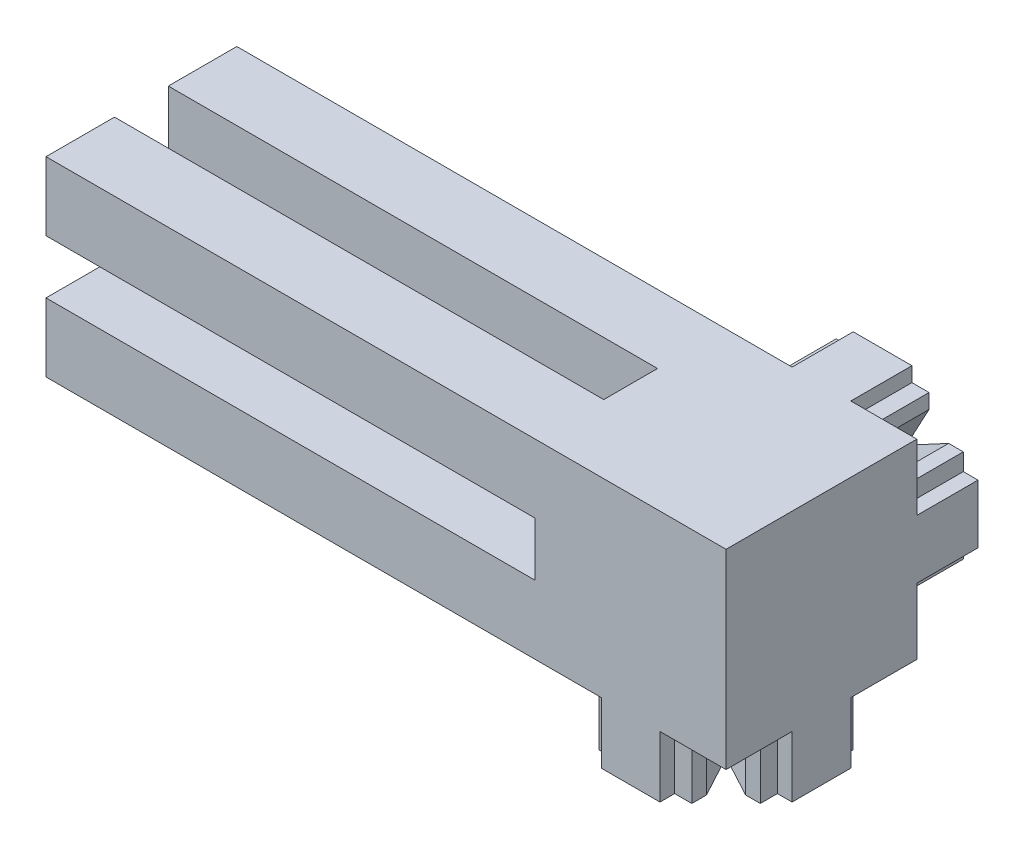
SolidWorks part; units mm, degrees
ref_plane "Front Plane" through (0, 0, 0) normal (0, 0, 1) x (1, 0, 0)
ref_plane "Top Plane" through (0, 0, 0) normal (0, 1, 0) x (1, 0, 0)
ref_plane "Right Plane" through (0, 0, 0) normal (1, 0, 0) x (0, 0, -1)
sketch "Sketch1" plane through (0, 0, 0) normal (0, 1, 0) x (1, 0, 0)
  line L0 (6.858, 0) -> (12.954, 0)
  line L1 (0, 0) -> (19.812, 0)
  line L2 (0, 0) -> (0, -19.812)
  line L3 (0, -19.812) -> (19.812, -19.812)
  line L4 (19.812, 0) -> (19.812, -19.812)
  line L5 (6.858, 0) -> (6.858, -1.524)
  line L6 (6.858, -1.524) -> (5.08, -1.524)
  line L7 (5.08, -1.524) -> (5.08, -3.048)
  line L8 (6.858, -6.35) -> (12.954, -6.35)
  line L9 (9.906, -7.62) -> (9.906, -6.35)
  line L10 (5.08, -3.048) -> (6.858, -6.35)
  line L11 (14.732, -3.048) -> (12.954, -6.35)
  line L12 (14.732, -1.524) -> (14.732, -3.048)
  line L13 (12.954, -1.524) -> (14.732, -1.524)
  line L14 (12.954, 0) -> (12.954, -1.524)
  line L15 (12.954, 0) -> (19.812, 0)
  line L16 (12.954, 0) -> (19.812, 0)
  line L17 (19.812, -6.858) -> (18.288, -6.858)
  line L18 (18.288, -6.858) -> (18.288, -5.08)
  line L19 (18.288, -5.08) -> (16.764, -5.08)
  line L20 (16.764, -5.08) -> (13.462, -6.858)
  line L21 (13.462, -6.858) -> (13.462, -12.954)
  line L22 (16.764, -14.732) -> (13.462, -12.954)
  line L23 (18.288, -14.732) -> (16.764, -14.732)
  line L24 (18.288, -12.954) -> (18.288, -14.732)
  line L25 (19.812, -12.954) -> (18.288, -12.954)
  line L26 (19.812, -6.858) -> (19.812, -12.954)
  line L27 (12.954, -19.812) -> (12.954, -18.288)
  line L28 (12.954, -18.288) -> (14.732, -18.288)
  line L29 (14.732, -18.288) -> (14.732, -16.764)
  line L30 (14.732, -16.764) -> (12.954, -13.462)
  line L31 (12.954, -13.462) -> (6.858, -13.462)
  line L32 (5.08, -16.764) -> (6.858, -13.462)
  line L33 (5.08, -18.288) -> (5.08, -16.764)
  line L34 (6.858, -18.288) -> (5.08, -18.288)
  line L35 (6.858, -19.812) -> (6.858, -18.288)
  line L36 (12.954, -19.812) -> (6.858, -19.812)
  line L37 (0, -12.954) -> (1.524, -12.954)
  line L38 (1.524, -12.954) -> (1.524, -14.732)
  line L39 (1.524, -14.732) -> (3.048, -14.732)
  line L40 (3.048, -14.732) -> (6.35, -12.954)
  line L41 (6.35, -12.954) -> (6.35, -6.858)
  line L42 (3.048, -5.08) -> (6.35, -6.858)
  line L43 (1.524, -5.08) -> (3.048, -5.08)
  line L44 (1.524, -6.858) -> (1.524, -5.08)
  line L45 (0, -6.858) -> (1.524, -6.858)
  line L46 (0, -12.954) -> (0, -6.858)
  circle A0 centre (9.906, -9.906) radius 2.286
  point P8 (9.906, 0)
  point P17 (9.906, -6.35)
  point P18 (5.08, -2.286)
  point P22 (14.732, -2.286)
  point P56 (9.906, -9.906)
  dimension "D7" = 1.27
  dimension "D9" = 7.62
  dimension "D1" = 19.812
  dimension "D2" = 19.812
  dimension "D3" = 6.096
  dimension "D4" = 1.524
  dimension "D5" = 1.778
  dimension "D6" = 1.524
  dimension "D8" = 6.096
  dimension "D10" = 4
extrude "Boss-Extrude1" add sketch "Sketch1" along normal blind 19.812 contours L14 L0 L5 L6 L7 L10 L8 L11 L12 L13 | A0 L8 L10 L7 L6 L5 L1 L2 L45 L44 L43 L42 L41 L40 L39 L38 L37 L3 L35 L34 L33 L32 L31 L30 L29 L28 L27 L4 L25 L24 L23 L22 L21 L20 L19 L18 L17 L14 L13 L12 L11 | L25 L4 L17 L18 L19 L20 L21 L22 L23 L24 | A0 | L35 L3 L27 L28 L29 L30 L31 L32 L33 L34 | L45 L2 L37 L38 L39 L40 L41 L42 L43 L44 region at (9.906, 0, 9.906) region at (6.5778, 0, 0.762) region at (9.906, 0, 3.193) region at (3.193, 0, 9.906) region at (16.619, 0, 9.906) region at (9.906, 0, 16.619)
extrude "Boss-Extrude2" add sketch "Sketch1<3>" against normal blind 6.35 contours L45 L2 L37 L38 L39 L40 L41 L42 L43 L44 | L35 L3 L27 L28 L29 L30 L31 L32 L33 L34 | L25 L4 L17 L18 L19 L20 L21 L22 L23 L24 | A0 region at (9.906, 0, 9.906) region at (3.193, 0, 9.906) region at (16.619, 0, 9.906) region at (9.906, 0, 16.619)
sketch "Sketch1<3>" plane through (0, 0, 0) normal (0, 1, 0) x (1, 0, 0) same geometry as "Sketch1"
sketch "Sketch3" plane through (0, 0, 0) normal (0, 0, -1) x (-1, 0, 0)
  line L0 (-19.812, 9.906) -> (0, 9.906)
  line L1 (-19.812, 19.812) -> (-19.812, 0) construction
  line L2 (0, 19.812) -> (0, 0) construction
  line L3 (-12.954, 19.812) -> (-6.858, 19.812)
  line L4 (-19.812, 19.812) -> (0, 19.812)
  line L5 (-19.812, 19.812) -> (-19.812, 0)
  line L6 (-19.812, 0) -> (0, 0)
  line L7 (0, 19.812) -> (0, 0)
  line L8 (-12.954, 19.812) -> (-12.954, 18.288)
  line L9 (-12.954, 18.288) -> (-14.732, 18.288)
  line L10 (-14.732, 18.288) -> (-14.732, 16.764)
  line L11 (-12.954, 13.462) -> (-6.858, 13.462)
  line L12 (-9.906, 12.192) -> (-9.906, 13.462)
  line L13 (-14.732, 16.764) -> (-12.954, 13.462)
  line L14 (-5.08, 16.764) -> (-6.858, 13.462)
  line L15 (-5.08, 18.288) -> (-5.08, 16.764)
  line L16 (-6.858, 18.288) -> (-5.08, 18.288)
  line L17 (-6.858, 19.812) -> (-6.858, 18.288)
  line L18 (-6.858, 19.812) -> (0, 19.812)
  line L19 (-6.858, 19.812) -> (0, 19.812)
  line L20 (0, 12.954) -> (-1.524, 12.954)
  line L21 (-1.524, 12.954) -> (-1.524, 14.732)
  line L22 (-1.524, 14.732) -> (-3.048, 14.732)
  line L23 (-3.048, 14.732) -> (-6.35, 12.954)
  line L24 (-6.35, 12.954) -> (-6.35, 6.858)
  line L25 (-3.048, 5.08) -> (-6.35, 6.858)
  line L26 (-1.524, 5.08) -> (-3.048, 5.08)
  line L27 (-1.524, 6.858) -> (-1.524, 5.08)
  line L28 (0, 6.858) -> (-1.524, 6.858)
  line L29 (0, 12.954) -> (0, 6.858)
  line L30 (-6.858, 0) -> (-6.858, 1.524)
  line L31 (-6.858, 1.524) -> (-5.08, 1.524)
  line L32 (-5.08, 1.524) -> (-5.08, 3.048)
  line L33 (-5.08, 3.048) -> (-6.858, 6.35)
  line L34 (-6.858, 6.35) -> (-12.954, 6.35)
  line L35 (-14.732, 3.048) -> (-12.954, 6.35)
  line L36 (-14.732, 1.524) -> (-14.732, 3.048)
  line L37 (-12.954, 1.524) -> (-14.732, 1.524)
  line L38 (-12.954, 0) -> (-12.954, 1.524)
  line L39 (-6.858, 0) -> (-12.954, 0)
  line L40 (-19.812, 6.858) -> (-18.288, 6.858)
  line L41 (-18.288, 6.858) -> (-18.288, 5.08)
  line L42 (-18.288, 5.08) -> (-16.764, 5.08)
  line L43 (-16.764, 5.08) -> (-13.462, 6.858)
  line L44 (-13.462, 6.858) -> (-13.462, 12.954)
  line L45 (-16.764, 14.732) -> (-13.462, 12.954)
  line L46 (-18.288, 14.732) -> (-16.764, 14.732)
  line L47 (-18.288, 12.954) -> (-18.288, 14.732)
  line L48 (-19.812, 12.954) -> (-18.288, 12.954)
  line L49 (-19.812, 6.858) -> (-19.812, 12.954)
  circle A0 centre (-9.906, 9.906) radius 2.286
  point P6 (0, 0)
  point P14 (-9.906, 19.812)
  point P23 (-9.906, 13.462)
  point P24 (-14.732, 17.526)
  point P28 (-5.08, 17.526)
  point P59 (-9.906, 9.906)
  line M3 (0, 19.812) -> (-19.812, 19.812)
  line M4 (-19.812, 19.812) -> (-19.812, 0)
  line M56 (0, 0) -> (0, 19.812)
extrude "Cut-Extrude1" cut sketch "Sketch1<5>" along normal blind 6.35 contours L14 L0 L5 L6 L7 L10 L8 L11 L12 L13 region at (9.906, 0, 3.193)
sketch "Sketch1<5>" plane through (0, 0, 0) normal (0, 1, 0) x (1, 0, 0) same geometry as "Sketch1"
extrude "Boss-Extrude3" add sketch "Sketch3" along normal blind 6.35 contours L43 L44 L0 L40 L41 L42 M4 | L48 L5 L0 L44 L45 L46 L47 | L17 L8 L9 L10 L13 L11 L14 L15 L16 M3 | L0 A0 | L0 A0 | L28 L7 L0 L24 L25 L26 L27 | L23 L24 L0 L20 L21 L22 M56 region at (16.619, 11.9401, 0) region at (16.619, 7.8719, 0) region at (9.906, 10.8762, 0) region at (9.906, 8.9358, 0) region at (9.906, 16.619, 0) region at (3.193, 11.9401, 0) region at (3.193, 7.8719, 0)
sketch "Sketch4" plane through (0, 0, 0) normal (-1, 0, 0) x (0, 0, 1)
  line L0 (9.906, 19.812) -> (9.906, 0)
  line L1 (0, 19.812) -> (7.112, 19.812)
  line L2 (0, 19.812) -> (0, 12.7)
  line L3 (0, 12.7) -> (7.112, 12.7)
  line L4 (7.112, 19.812) -> (7.112, 12.7)
  line L5 (0, 19.812) -> (19.812, 19.812) construction
  line L6 (19.812, 9.906) -> (0, 9.906)
  line L7 (19.812, 19.812) -> (19.812, 0) construction
  line L8 (19.812, 19.812) -> (12.7, 19.812)
  line L9 (19.812, 19.812) -> (19.812, 12.7)
  line L10 (19.812, 12.7) -> (12.7, 12.7)
  line L11 (12.7, 19.812) -> (12.7, 12.7)
  line L12 (19.812, 0) -> (19.812, 7.112)
  line L13 (19.812, 0) -> (12.7, 0)
  line L14 (19.812, 7.112) -> (12.7, 7.112)
  line L15 (12.7, 0) -> (12.7, 7.112)
  line L16 (0, 0) -> (7.112, 0)
  line L17 (0, 0) -> (0, 7.112)
  line L18 (0, 7.112) -> (7.112, 7.112)
  line L19 (7.112, 0) -> (7.112, 7.112)
  line M11 (0, 0) -> (6.858, 0)
  line M15 (12.954, 0) -> (19.812, 0)
  line M16 (19.812, 0) -> (19.812, 19.812)
  line M17 (19.812, 19.812) -> (0, 19.812)
  line M18 (0, 19.812) -> (0, 12.954)
  line M22 (0, 6.858) -> (0, 0)
  dimension "D1" = 7.112
  dimension "D2" = 7.112
extrude "Boss-Extrude4" add sketch "Sketch4" along normal blind 50.8 contours L4 L3 M17 M18 | L19 L18 M11 M22 | L15 L14 M15 M16 | L11 L10 M17 M16 region at (0, 3.556, 16.256) region at (0, 16.256, 3.556) region at (0, 16.256, 16.256) region at (0, 3.556, 3.556)
